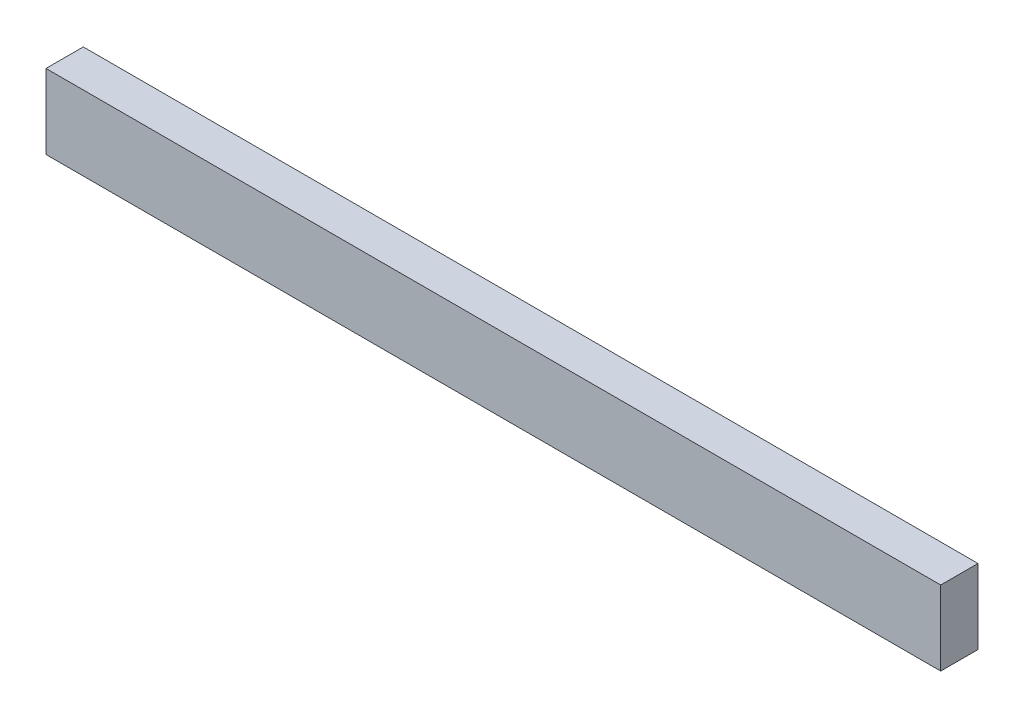
SolidWorks part; units mm, degrees
ref_plane "Front Plane" through (0, 0, 0) normal (0, 0, 1) x (1, 0, 0)
ref_plane "Top Plane" through (0, 0, 0) normal (0, 1, 0) x (1, 0, 0)
ref_plane "Right Plane" through (0, 0, 0) normal (1, 0, 0) x (0, 0, -1)
sketch "Sketch1" plane through (0, 0, 0) normal (0, 0, 1) x (1, 0, 0)
  line L1 (-609.6, 50.8) -> (609.6, 50.8)
  line L2 (-609.6, 50.8) -> (-609.6, -50.8)
  line L3 (-609.6, -50.8) -> (609.6, -50.8)
  line L4 (609.6, 50.8) -> (609.6, -50.8)
  line L5 (-609.6, 50.8) -> (609.6, -50.8) construction
  line L6 (-609.6, -50.8) -> (609.6, 50.8) construction
  point P0 (0, 0)
  dimension "D1" = 1219.2
  dimension "D2" = 101.6
extrude "Boss-Extrude1" add sketch "Sketch1" along normal blind 25.4 and the other way blind 25.4
